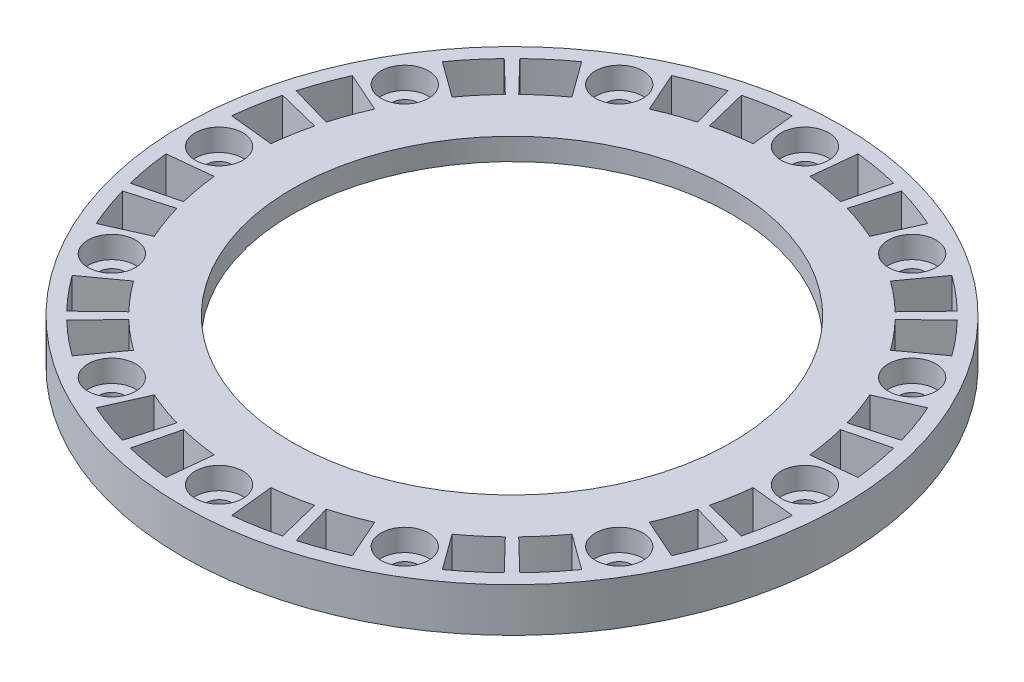
SolidWorks part; units mm, degrees
ref_plane "Front Plane" through (0, 0, 0) normal (0, 0, 1) x (1, 0, 0)
ref_plane "Top Plane" through (0, 0, 0) normal (0, 1, 0) x (1, 0, 0)
ref_plane "Right Plane" through (0, 0, 0) normal (1, 0, 0) x (0, 0, -1)
sketch "Sketch1" plane through (0, 0, 0) normal (0, 1, 0) x (1, 0, 0)
  line L0 (0, 0) -> (0, 52.0165) construction
  circle A0 centre (0, 0) radius 45
  circle A1 centre (0, 0) radius 30
  circle A2 centre (0, 0) radius 40 construction
  circle A3 centre (0, 40) radius 1.75
  circle A4 centre (0, 0) radius 35 construction
  circle A5 centre (20, 34.641) radius 1.75
  circle A6 centre (34.641, 20) radius 1.75
  circle A7 centre (40, 0) radius 1.75
  circle A8 centre (34.641, -20) radius 1.75
  circle A9 centre (20, -34.641) radius 1.75
  circle A10 centre (0, -40) radius 1.75
  circle A11 centre (-20, -34.641) radius 1.75
  circle A12 centre (-34.641, -20) radius 1.75
  circle A13 centre (-40, 0) radius 1.75
  circle A14 centre (-34.641, 20) radius 1.75
  circle A15 centre (-20, 34.641) radius 1.75
  point P21 (0, 0)
  point P34 (0, 0)
  point P48 (0, 0)
  point P72 (0, 0)
  dimension "D1" = 90
  dimension "D2" = 60
  dimension "D4" = 3.5
  dimension "D5" = 70
  dimension "D6" = 12
  dimension "D3" = 80
extrude "Boss-Extrude1" add sketch "Sketch1" along normal blind 6
sketch "Sketch2" plane through (0, 0, 0) normal (0, -1, 0) x (1, 0, 0)
  circle A0 centre (0, 0) radius 35.5
  dimension "D1" = 71
extrude "Cut-Extrude1" cut sketch "Sketch2" against normal blind 3
sketch "Sketch3" plane through (0, 6, 0) normal (0, 1, 0) x (1, 0, 0)
  line L0 (0, 0) -> (49.8808, 0) construction
  circle A0 centre (40, 0) radius 3.25
  circle A1 centre (34.641, -20) radius 3.25
  circle A2 centre (20, -34.641) radius 3.25
  circle A3 centre (0, -40) radius 3.25
  circle A4 centre (-20, -34.641) radius 3.25
  circle A5 centre (-34.641, -20) radius 3.25
  circle A6 centre (-40, 0) radius 3.25
  circle A7 centre (-34.641, 20) radius 3.25
  circle A8 centre (-20, 34.641) radius 3.25
  circle A9 centre (0, 40) radius 3.25
  circle A10 centre (20, 34.641) radius 3.25
  circle A11 centre (34.641, 20) radius 3.25
  point P30 (0, 0)
  dimension "D1" = 6.5
  dimension "D2" = 12
extrude "Cut-Extrude2" cut sketch "Sketch3" against normal blind 3
sketch "Sketch4" plane through (0, 0, 0) normal (0, -1, 0) x (1, 0, 0)
  line L0 (0, 0) -> (45, 0) construction
  line L1 (0, 0) -> (43.4667, -11.6469) construction
  line L2 (0, 0) -> (44.7535, -4.7038) construction
  line L3 (42.7644, -4.4947) -> (36.7973, -3.8676)
  line L4 (39.2825, -17.4897) -> (33.8012, -15.0493)
  line L5 (0, 0) -> (43.6633, -10.8865) construction
  line L6 (41.7227, -10.4026) -> (35.9009, -8.9511)
  line L7 (41.3343, -11.8524) -> (35.5667, -10.1986)
  line L8 (34.7877, -25.2748) -> (29.9336, -21.7481)
  line L9 (30.9316, -29.8703) -> (26.6156, -25.7024)
  line L10 (29.8703, -30.9316) -> (25.7024, -26.6156)
  line L11 (25.2748, -34.7877) -> (21.7481, -29.9336)
  line L12 (17.4897, -39.2825) -> (15.0493, -33.8012)
  line L13 (11.8524, -41.3343) -> (10.1986, -35.5667)
  line L14 (10.4026, -41.7227) -> (8.9511, -35.9009)
  line L15 (4.4947, -42.7644) -> (3.8676, -36.7973)
  line L16 (-4.4947, -42.7644) -> (-3.8676, -36.7973)
  line L17 (-10.4026, -41.7227) -> (-8.9511, -35.9009)
  line L18 (-11.8524, -41.3343) -> (-10.1986, -35.5667)
  line L19 (-17.4897, -39.2825) -> (-15.0493, -33.8012)
  line L20 (-25.2748, -34.7877) -> (-21.7481, -29.9336)
  line L21 (-29.8703, -30.9316) -> (-25.7024, -26.6156)
  line L22 (-30.9316, -29.8703) -> (-26.6156, -25.7024)
  line L23 (-34.7877, -25.2748) -> (-29.9336, -21.7481)
  line L24 (-39.2825, -17.4897) -> (-33.8012, -15.0493)
  line L25 (-41.3343, -11.8524) -> (-35.5667, -10.1986)
  line L26 (-41.7227, -10.4026) -> (-35.9009, -8.9511)
  line L27 (-42.7644, -4.4947) -> (-36.7973, -3.8676)
  line L28 (-42.7644, 4.4947) -> (-36.7973, 3.8676)
  line L29 (-41.7227, 10.4026) -> (-35.9009, 8.9511)
  line L30 (-41.3343, 11.8524) -> (-35.5667, 10.1986)
  line L31 (-39.2825, 17.4897) -> (-33.8012, 15.0493)
  line L32 (-34.7877, 25.2748) -> (-29.9336, 21.7481)
  line L33 (-30.9316, 29.8703) -> (-26.6156, 25.7024)
  line L34 (-29.8703, 30.9316) -> (-25.7024, 26.6156)
  line L35 (-25.2748, 34.7877) -> (-21.7481, 29.9336)
  line L36 (-17.4897, 39.2825) -> (-15.0493, 33.8012)
  line L37 (-11.8524, 41.3343) -> (-10.1986, 35.5667)
  line L38 (-10.4026, 41.7227) -> (-8.9511, 35.9009)
  line L39 (-4.4947, 42.7644) -> (-3.8676, 36.7973)
  line L40 (4.4947, 42.7644) -> (3.8676, 36.7973)
  line L41 (10.4026, 41.7227) -> (8.9511, 35.9009)
  line L42 (11.8524, 41.3343) -> (10.1986, 35.5667)
  line L43 (17.4897, 39.2825) -> (15.0493, 33.8012)
  line L44 (25.2748, 34.7877) -> (21.7481, 29.9336)
  line L45 (29.8703, 30.9316) -> (25.7024, 26.6156)
  line L46 (30.9316, 29.8703) -> (26.6156, 25.7024)
  line L47 (34.7877, 25.2748) -> (29.9336, 21.7481)
  line L48 (39.2825, 17.4897) -> (33.8012, 15.0493)
  line L49 (41.3343, 11.8524) -> (35.5667, 10.1986)
  line L50 (41.7227, 10.4026) -> (35.9009, 8.9511)
  line L51 (42.7644, 4.4947) -> (36.7973, 3.8676)
  circle A0 centre (0, 0) radius 45 construction
  circle A1 centre (40, 0) radius 3.25 construction
  arc A2 (42.7644, -4.4947) -> (41.7227, -10.4026) centre (0, 0) cw
  arc A3 (36.7973, -3.8676) -> (35.9009, -8.9511) centre (0, 0) cw
  arc A4 (41.3343, -11.8524) -> (39.2825, -17.4897) centre (0, 0) cw
  arc A5 (35.5667, -10.1986) -> (33.8012, -15.0493) centre (0, 0) cw
  arc A6 (34.7877, -25.2748) -> (30.9316, -29.8703) centre (0, 0) cw
  arc A7 (29.9336, -21.7481) -> (26.6156, -25.7024) centre (0, 0) cw
  arc A8 (29.8703, -30.9316) -> (25.2748, -34.7877) centre (0, 0) cw
  arc A9 (25.7024, -26.6156) -> (21.7481, -29.9336) centre (0, 0) cw
  arc A10 (17.4897, -39.2825) -> (11.8524, -41.3343) centre (0, 0) cw
  arc A11 (15.0493, -33.8012) -> (10.1986, -35.5667) centre (0, 0) cw
  arc A12 (10.4026, -41.7227) -> (4.4947, -42.7644) centre (0, 0) cw
  arc A13 (8.9511, -35.9009) -> (3.8676, -36.7973) centre (0, 0) cw
  arc A14 (-4.4947, -42.7644) -> (-10.4026, -41.7227) centre (0, 0) cw
  arc A15 (-3.8676, -36.7973) -> (-8.9511, -35.9009) centre (0, 0) cw
  arc A16 (-11.8524, -41.3343) -> (-17.4897, -39.2825) centre (0, 0) cw
  arc A17 (-10.1986, -35.5667) -> (-15.0493, -33.8012) centre (0, 0) cw
  arc A18 (-25.2748, -34.7877) -> (-29.8703, -30.9316) centre (0, 0) cw
  arc A19 (-21.7481, -29.9336) -> (-25.7024, -26.6156) centre (0, 0) cw
  arc A20 (-30.9316, -29.8703) -> (-34.7877, -25.2748) centre (0, 0) cw
  arc A21 (-26.6156, -25.7024) -> (-29.9336, -21.7481) centre (0, 0) cw
  arc A22 (-39.2825, -17.4897) -> (-41.3343, -11.8524) centre (0, 0) cw
  arc A23 (-33.8012, -15.0493) -> (-35.5667, -10.1986) centre (0, 0) cw
  arc A24 (-41.7227, -10.4026) -> (-42.7644, -4.4947) centre (0, 0) cw
  arc A25 (-35.9009, -8.9511) -> (-36.7973, -3.8676) centre (0, 0) cw
  arc A26 (-42.7644, 4.4947) -> (-41.7227, 10.4026) centre (0, 0) cw
  arc A27 (-36.7973, 3.8676) -> (-35.9009, 8.9511) centre (0, 0) cw
  arc A28 (-41.3343, 11.8524) -> (-39.2825, 17.4897) centre (0, 0) cw
  arc A29 (-35.5667, 10.1986) -> (-33.8012, 15.0493) centre (0, 0) cw
  arc A30 (-34.7877, 25.2748) -> (-30.9316, 29.8703) centre (0, 0) cw
  arc A31 (-29.9336, 21.7481) -> (-26.6156, 25.7024) centre (0, 0) cw
  arc A32 (-29.8703, 30.9316) -> (-25.2748, 34.7877) centre (0, 0) cw
  arc A33 (-25.7024, 26.6156) -> (-21.7481, 29.9336) centre (0, 0) cw
  arc A34 (-17.4897, 39.2825) -> (-11.8524, 41.3343) centre (0, 0) cw
  arc A35 (-15.0493, 33.8012) -> (-10.1986, 35.5667) centre (0, 0) cw
  arc A36 (-10.4026, 41.7227) -> (-4.4947, 42.7644) centre (0, 0) cw
  arc A37 (-8.9511, 35.9009) -> (-3.8676, 36.7973) centre (0, 0) cw
  arc A38 (4.4947, 42.7644) -> (10.4026, 41.7227) centre (0, 0) cw
  arc A39 (3.8676, 36.7973) -> (8.9511, 35.9009) centre (0, 0) cw
  arc A40 (11.8524, 41.3343) -> (17.4897, 39.2825) centre (0, 0) cw
  arc A41 (10.1986, 35.5667) -> (15.0493, 33.8012) centre (0, 0) cw
  arc A42 (25.2748, 34.7877) -> (29.8703, 30.9316) centre (0, 0) cw
  arc A43 (21.7481, 29.9336) -> (25.7024, 26.6156) centre (0, 0) cw
  arc A44 (30.9316, 29.8703) -> (34.7877, 25.2748) centre (0, 0) cw
  arc A45 (26.6156, 25.7024) -> (29.9336, 21.7481) centre (0, 0) cw
  arc A46 (39.2825, 17.4897) -> (41.3343, 11.8524) centre (0, 0) cw
  arc A47 (33.8012, 15.0493) -> (35.5667, 10.1986) centre (0, 0) cw
  arc A48 (41.7227, 10.4026) -> (42.7644, 4.4947) centre (0, 0) cw
  arc A49 (35.9009, 8.9511) -> (36.7973, 3.8676) centre (0, 0) cw
  point P111 (0, 0)
  dimension "D3" = 6.5
  dimension "D4" = 43
  dimension "D5" = 37
  dimension "D1" = 15
  dimension "D2" = 9
  dimension "D6" = 1
  dimension "D7" = 12
extrude "Cut-Extrude3" cut sketch "Sketch4" against normal through all
